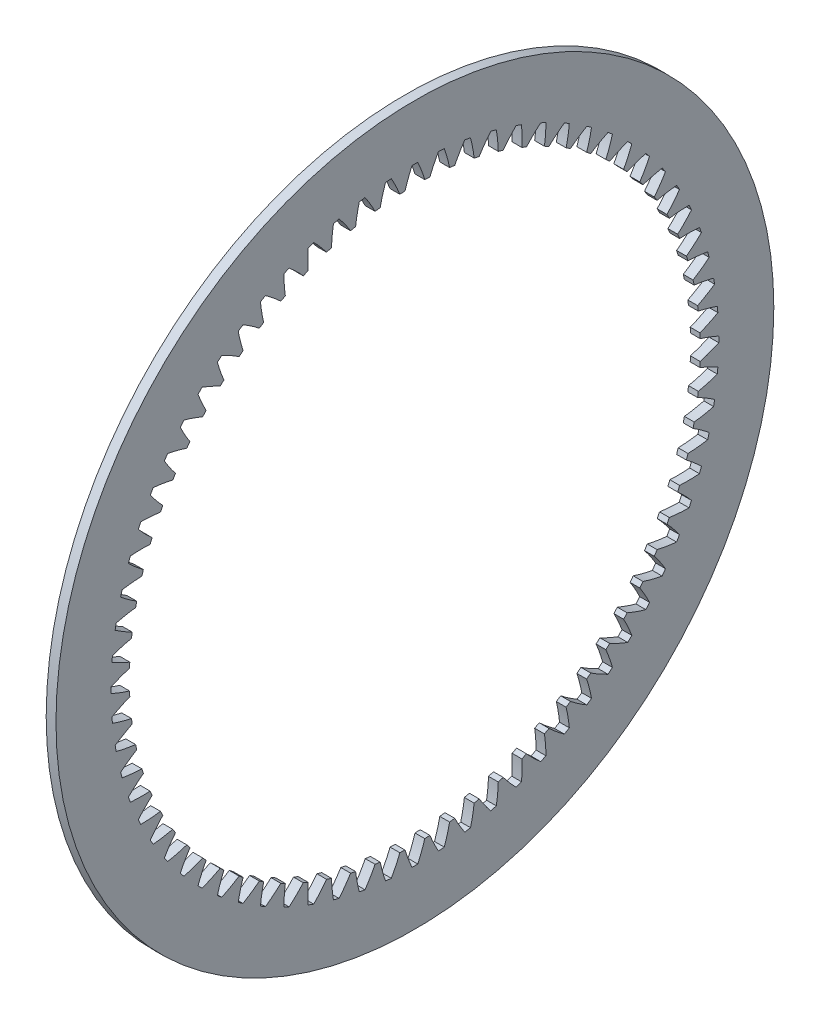
SolidWorks part; units mm, degrees
ref_plane "Plane1" through (0, 0, 0) normal (0, 0, 1) x (1, 0, 0)
ref_plane "Plane2" through (0, 0, 0) normal (0, 1, 0) x (1, 0, 0)
ref_plane "Plane3" through (0, 0, 0) normal (1, 0, 0) x (0, 0, -1)
sketch "HoldingSke" plane through (0, 0, 0) normal (0, 1, 0) x (1, 0, 0)
  line L0 (0, 0) -> (0.1236, -0.3804)
  line L1 (-15, 0) -> (100, 0) construction
  line L2 (0, 0) -> (-2.1039, 2.3779)
  line L3 (0, 0) -> (-11.863, 4.5341)
  line L4 (0, 0) -> (2.6687, 8.2133)
  line L5 (0, 0) -> (-23.7986, -8.8762)
  line L6 (0, 0) -> (-10.5278, -7.1032)
  line L7 (-2.1039, 2.3779) -> (3.3635, 27.1825)
  line L8 (-76.2, 4.8779) -> (-54.61, 4.8779)
  line L9 (-71.009, 38.7566) -> (-53.1078, 45.2721)
  line L10 (-76.2, 71.12) -> (104.1128, 71.12)
  line L11 (0, 0) -> (-3, 0)
  line L12 (-76.2, 101.6) -> (-76.113, 101.6)
  line L13 (24.9733, 27.94) -> (52.9518, 28.4284)
  line L14 (24.9733, 27.94) -> (24.9743, 27.94)
  line L15 (24.9733, 27.94) -> (100.4006, 29.5858)
  circle A0 centre (0, 0) radius 110
  circle A1 centre (0, 0) radius 12.7
  circle A2 centre (0, 0) radius 12.7
  dimension "Num_teeth" = 72
  dimension "Pitch_radius" = 180.3128
  dimension "Width" = 3
  dimension "Diameter" = 220
sketch "BasProSke" plane through (0, 0, 0) normal (0, 1, 0) x (1, 0, 0)
  line L0 (-10, 0) -> (60, 0) construction
  line L1 (0, 87.5) -> (0, 110)
  line L2 (0, 87.5) -> (3, 87.5)
  line L3 (3, 87.5) -> (3, 110)
  line L4 (3, 110) -> (0, 110)
  dimension "Thickness" = 3
  dimension "Diameter" = 220
revolve "Base-Revolve" add sketch "BasProSke" angle 360 about L0
sketch "TooCutSke" plane through (0, 0, 0) normal (1, 0, 0) x (0, 0, -1)
  line L3 (2.1808, 89.9736) -> (2.1808, 53.6633) construction
  line L4 (0, 0) -> (0, 59.563) construction
  line L5 (0, 0) -> (-2.9804, 68.2625) construction
  line L6 (-40.0527, 74.4389) -> (34.4867, 77.6933) construction
  circle A0 centre (0, 0) radius 90 construction
  circle A1 centre (0, 0) radius 93.126 construction
  circle A2 centre (0, 0) radius 76.1151 construction
  circle A3 centre (0, 0) radius 87.4746 construction
  arc A4 (3.0337, 87.422) -> (0.8856, 93.1218) centre (-40.0527, 74.4389) ccw
  arc A5 (3.0337, 87.422) -> (-3.0337, 87.422) centre (0, 0) ccw
  arc A6 (0.8856, 93.1218) -> (-0.8856, 93.1218) centre (0, 0) ccw
  arc A7 (-0.8856, 93.1218) -> (-3.0337, 87.422) centre (40.0527, 74.4389) ccw
extrude "ToothCut" cut sketch "TooCutSke" along normal through all
fillet "Breaks" [suppressed] radius 0.25
fillet "RootFillets" [suppressed] radius 0.626
pattern_circular "TeethCuts" count 72 every 5 about axis through (-10, 0, 0) along (1, 0, 0) of "RootFillets", "Breaks", "ToothCut"
equation "' \"Module@HoldingSke\" = 6.35"
equation "' \"Num_teeth@HoldingSke\" = 24"
equation "' \"Ap@HoldingSke\" =  14.5"
equation "' \"Ap@HoldingSke\" = 14.5"
equation "' \"Width@HoldingSke\" = 12"
equation "' \"Diameter@HoldingSke\" = 8 * 25.4"
equation "' \"Show_teeth@HoldingSke\" = 100"
equation "' \"Backlash@HoldingSke\" = 0.009 * 25.4"
equation "' \"Addendum_fac@HoldingSke\" = 1.0"
equation "' \"Dedendum_fac@HoldingSke\" = 1.25"
equation "' \"Dedendum_add@HoldingSke\" = 0.00005 * 25.4"
equation "' \"Clearance_fac@HoldingSke\" = 0.25"
equation "\"Pitch@HoldingSke\" = 1 / \"Module@HoldingSke\" "
equation "\"Overcut_dia@TooCutSke\" = (\"Num_teeth@HoldingSke\" - 2 * \"Addendum_fac@HoldingSke\") / \"Pitch@HoldingSke\" - 0.002 * 25.4"
equation "\"Pitch_dia@TooCutSke\" = \"Num_teeth@HoldingSke\" / \"Pitch@HoldingSke\""
equation "\"Base_dia@TooCutSke\" = \"Num_teeth@HoldingSke\" / \"Pitch@HoldingSke\" * cos((\"Ap@HoldingSke\"  * 3.14159265 / 180)) * 0.90"
equation "\"Root_dia@TooCutSke\" = \"Num_teeth@HoldingSke\"  / \"Pitch@HoldingSke\" + 2 *  \"Dedendum_fac@HoldingSke\"/ \"Pitch@HoldingSke\" + \"Dedendum_add@HoldingSke\" * 2"
equation "\"Half_ang@TooCutSke\" = 180 / \"Num_teeth@HoldingSke\""
equation "\"Half_CT@TooCutSke\" = \"Num_teeth@HoldingSke\" / \"Pitch@HoldingSke\" * sin((3.14159265 / 2 / \"Num_teeth@HoldingSke\")) / 2 + 10 * \"Backlash@HoldingSke\" / 4"
equation "\"Flank_rad@TooCutSke\" = \"Num_teeth@HoldingSke\" / \"Pitch@HoldingSke\" / 4"
equation "\"Radius@RootFillets\"= \"Clearance_fac@HoldingSke\" / \"Pitch@HoldingSke\" + \"Dedendum_add@HoldingSke\""
equation "\"Break_rad@Breaks\" = 0.02 / \"Pitch@HoldingSke\" * 5"
equation "\"Num_teeth@TeethCuts\" = int( \"Show_teeth@HoldingSke\" ) + 1"
equation "\"Num_teeth@TeethCuts\" = ((sgn( \"Num_teeth@TeethCuts\" - \"Num_teeth@HoldingSke\" )-1)*( \"Num_teeth@TeethCuts\" - \"Num_teeth@HoldingSke\" ))/-2+ \"Num_teeth@HoldingSke\""
equation "\"Num_teeth@TeethCuts\" = ((sgn( \"Num_teeth@TeethCuts\" - 2.0)+1)*( \"Num_teeth@TeethCuts\" - 2.0))/2 +2.0"
equation "\"Angle@TeethCuts\" = 360.0 / \"Num_teeth@HoldingSke\""
equation "\"Diameter@BasProSke\" = \"Num_teeth@HoldingSke\"  / \"Pitch@HoldingSke\" + 2 *  \"Dedendum_fac@HoldingSke\"/ \"Pitch@HoldingSke\" + \"Dedendum_add@HoldingSke\" * 2 + 0.002 * 25.4"
equation "\"Diameter@BasProSke\" = ((sgn( \"Diameter@BasProSke\"  - \"Diameter@HoldingSke\" )+1)*( \"Diameter@BasProSke\"  - \"Diameter@HoldingSke\" ))/2 + \"Diameter@HoldingSke\""
equation "\"Inside_diameter@BasProSke\" =  (\"Num_teeth@HoldingSke\" - 2 * \"Addendum_fac@HoldingSke\") / \"Pitch@HoldingSke\" "
equation "\"Thickness@BasProSke\"  = \"Width@HoldingSke\""
